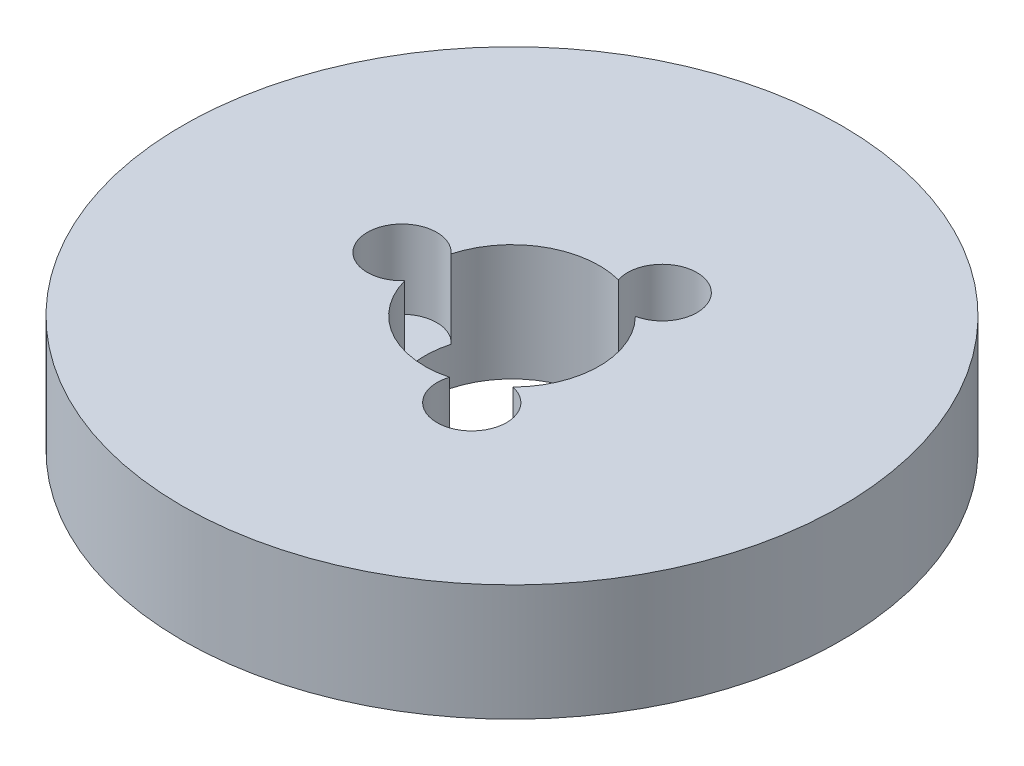
SolidWorks part; units mm, degrees
ref_plane "Front Plane" through (0, 0, 0) normal (0, 0, 1) x (1, 0, 0)
ref_plane "Top Plane" through (0, 0, 0) normal (0, 1, 0) x (1, 0, 0)
ref_plane "Right Plane" through (0, 0, 0) normal (1, 0, 0) x (0, 0, -1)
sketch "Sketch1" plane through (0, 0, 0) normal (0, 1, 0) x (1, 0, 0)
  circle A0 centre (0, 0) radius 85
  dimension "FLANGE_OD" = 170
extrude "Boss-Extrude1" add sketch "Sketch1" along normal blind 30
sketch "Sketch2" plane through (0, 0, 0) normal (0, 1, 0) x (1, 0, 0)
  circle A0 centre (0, 0) radius 22.5
  dimension "BORE_D" = 45
extrude "Cut-Extrude1" cut sketch "Sketch2" along normal through all
sketch "Sketch3" plane through (0, 30, 0) normal (0, 1, 0) x (1, 0, 0)
  circle A0 centre (0, 0) radius 28.3625 construction
  circle A1 centre (-28.3625, 0) radius 8.9637
  dimension "BOLT_D" = 17.9274
  dimension "BOLT_PCD" = 56.725
extrude "Cut-Extrude2" cut sketch "Sketch3" against normal blind 20.1735
pattern_circular "CirPattern1" count 3 over 360 about axis through (0, 0, 0) along (0, 1, 0) of "Cut-Extrude2"
